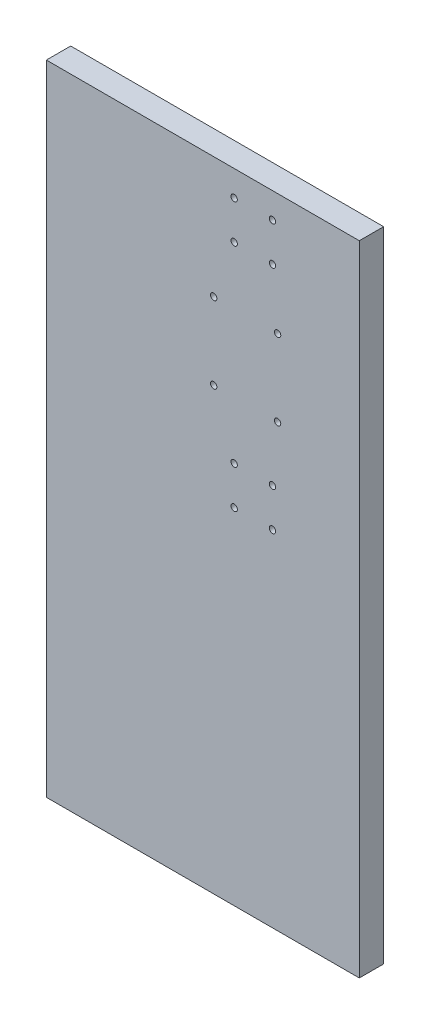
SolidWorks part; units mm, degrees
ref_plane "Front Plane" through (0, 0, 0) normal (0, 0, 1) x (1, 0, 0)
ref_plane "Top Plane" through (0, 0, 0) normal (0, 1, 0) x (1, 0, 0)
ref_plane "Right Plane" through (0, 0, 0) normal (1, 0, 0) x (0, 0, -1)
sketch "Sketch1" plane through (0, 0, 0) normal (0, 0, 1) x (1, 0, 0)
  line L1 (-245.05, 250) -> (0, 250)
  line L2 (-245.05, 250) -> (-245.05, -250)
  line L3 (-245.05, -250) -> (0, -250)
  line L4 (0, 250) -> (0, -250)
  dimension "D1" = 500
  dimension "D2" = 245.05
extrude "Boss-Extrude1" add sketch "Sketch1" along normal blind 19.05
hole_wizard "Ø5.0mm Dowel Hole1" positions "Sketch2" profile "Sketch3" hole size "Ø5.0" standard "ANSI Metric"
sketch "Sketch2" plane through (0, 0, 19.05) normal (0, 0, 1) x (1, 0, 0)
  point P0 (-68, 20)
  point P3 (-98, 20)
  point P6 (-68, 50)
  point P9 (-98, 50)
  point P12 (-64, 95)
  point P15 (-114, 95)
  point P18 (-64, 155)
  point P21 (-114, 155)
  point P24 (-68, 200)
  point P27 (-98, 200)
  point P30 (-68, 230)
  point P33 (-98, 230)
sketch "Sketch3" plane through (-68, 20, 19.05) normal (1, 0, 0) x (0, -1, 0)
  line L0 (0, 0) -> (0, 30)
  line L1 (0, 30) -> (2.5, 28.4978)
  line L2 (2.5, 28.4978) -> (2.5, 0)
  line L5 (2.5, 0) -> (0, 0)
  line L10 (0, 30) -> (-2.5, 28.4978) construction
  line L11 (0, -6.35) -> (0, 107.95) construction
  dimension "Hole Dia." = 5
  dimension "Hole Depth" = 30
  dimension "Drill Angle" = 118
